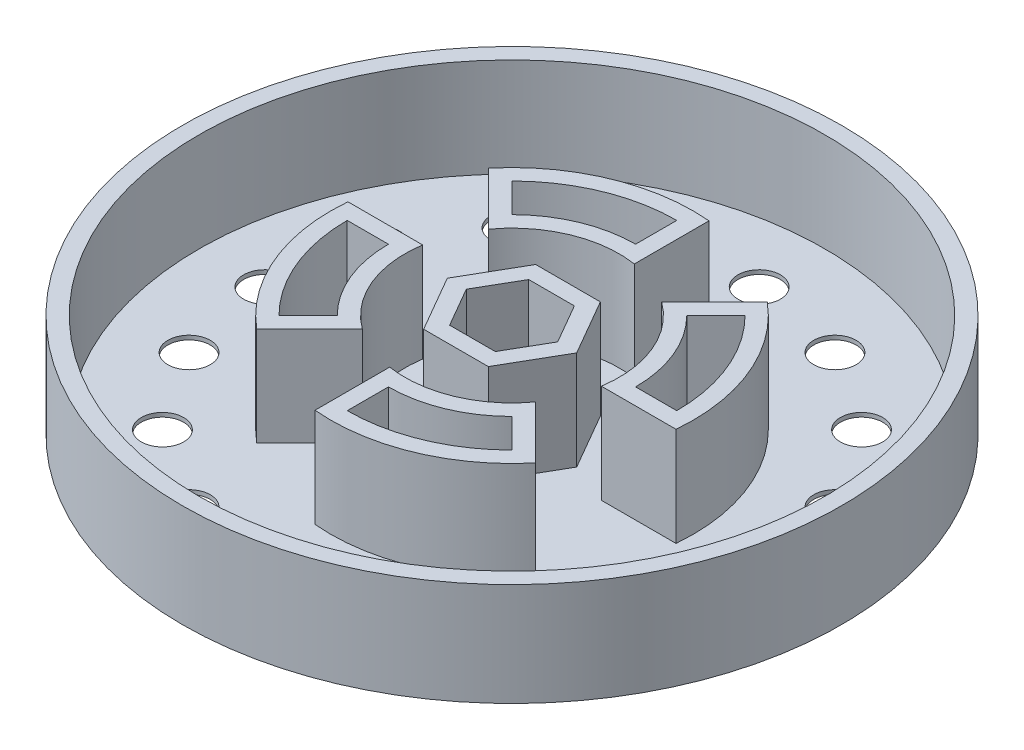
SolidWorks part; units mm, degrees
ref_plane "Front Plane" through (0, 0, 0) normal (0, 0, 1) x (1, 0, 0)
ref_plane "Top Plane" through (0, 0, 0) normal (0, 1, 0) x (1, 0, 0)
ref_plane "Right Plane" through (0, 0, 0) normal (1, 0, 0) x (0, 0, -1)
sketch "Sketch1" plane through (0, 0, 0) normal (0, 1, 0) x (1, 0, 0)
  circle A0 centre (0, 0) radius 50.8
  dimension "D1" = 101.6
extrude "Boss-Extrude1" add sketch "Sketch1" along normal blind 15.875
sketch "Sketch4" plane through (0, 15.875, 0) normal (0, 1, 0) x (1, 0, 0)
  line L0 (-3.5195, 6.096) -> (3.5195, 6.096)
  line L1 (3.5195, 6.096) -> (7.0391, 0)
  line L2 (7.0391, 0) -> (3.5195, -6.096)
  line L3 (3.5195, -6.096) -> (-3.5195, -6.096)
  line L4 (-3.5195, -6.096) -> (-7.0391, 0)
  line L5 (-7.0391, 0) -> (-3.5195, 6.096)
  point P7 (0, 6.096)
  dimension "D1" = 120
  dimension "D2" = 12.192
extrude "Cut-Extrude2" cut sketch "Sketch4" against normal blind 15.24 contours L5 L0 L1 L2 L3 L4
sketch "Sketch5" plane through (0, 0.635, 0) normal (0, 1, 0) x (1, 0, 0)
  circle A0 centre (0, 0) radius 4.191
  dimension "D1" = 8.382
extrude "Cut-Extrude3" cut sketch "Sketch5" against normal through all contours A0
sketch "Sketch6" plane through (0, 15.875, 0) normal (0, 1, 0) x (1, 0, 0)
  line L0 (0, 0) -> (0, 25.4)
  line L1 (0, 0) -> (17.9605, 17.9605)
  line L2 (0, 0) -> (25.4, 0)
  line L3 (0, 0) -> (17.9605, -17.9605)
  line L4 (0, 0) -> (0, -25.4)
  line L5 (0, 0) -> (-17.9605, -17.9605)
  line L6 (0, 0) -> (-25.4, 0)
  line L7 (0, 0) -> (-17.9605, 17.9605)
  circle A0 centre (0, 0) radius 25.4
  circle A1 centre (0, 0) radius 19.05
  point P15 (0, 0)
  dimension "D1" = 38.1
  dimension "D2" = 50.8
  dimension "D3" = 45
  dimension "D4" = 4
extrude "Cut-Extrude4" cut sketch "Sketch6" against normal through all contours A1 L0 A0 L7 | A1 L2 A0 L1 | A1 L4 A0 L3 | A1 L6 A0 L5 region at (-8.3446, 15.875, -20.1456) region at (20.1456, 15.875, -8.3446) region at (8.3446, 15.875, 20.1456) region at (-20.1456, 15.875, 8.3446)
sketch "Sketch7" plane through (0, 15.875, 0) normal (0, 1, 0) x (1, 0, 0)
  line L27 (16.3134, -2.54) -> (27.8243, -2.54)
  line L28 (17.8787, 21.4708) -> (9.7393, 13.3314)
  line L29 (2.54, 16.3134) -> (2.54, 27.8243)
  line L30 (-21.4708, 17.8787) -> (-13.3314, 9.7393)
  line L31 (2.54, 16.3134) -> (2.54, 27.8243)
  line L32 (-21.4708, 17.8787) -> (-13.3314, 9.7393)
  line L33 (-2.54, -16.3134) -> (-2.54, -27.8243)
  line L34 (21.4708, -17.8787) -> (13.3314, -9.7393)
  line L35 (-16.3134, 2.54) -> (-27.8243, 2.54)
  line L36 (-17.8787, -21.4708) -> (-9.7393, -13.3314)
  line L64 (9.972, 0) -> (4.986, 8.636)
  line L65 (4.986, -8.636) -> (9.972, 0)
  line L66 (-4.986, -8.636) -> (4.986, -8.636)
  line L67 (-9.972, 0) -> (-4.986, -8.636)
  line L68 (-4.986, 8.636) -> (-9.972, 0)
  line L69 (4.986, 8.636) -> (-4.986, 8.636)
  line L70 (9.972, 0) -> (4.986, 8.636)
  line L71 (4.986, -8.636) -> (9.972, 0)
  line L72 (-4.986, -8.636) -> (4.986, -8.636)
  line L73 (-9.972, 0) -> (-4.986, -8.636)
  line L74 (-4.986, 8.636) -> (-9.972, 0)
  line L75 (4.986, 8.636) -> (-4.986, 8.636)
  arc A28 (27.8243, -2.54) -> (17.8787, 21.4708) centre (0, 0) ccw
  arc A29 (16.3134, -2.54) -> (9.7393, 13.3314) centre (0, 0) ccw
  arc A30 (2.54, 16.3134) -> (-13.3314, 9.7393) centre (0, 0) ccw
  arc A31 (2.54, 27.8243) -> (-21.4708, 17.8787) centre (0, 0) ccw
  arc A32 (2.54, 16.3134) -> (-13.3314, 9.7393) centre (0, 0) ccw
  arc A33 (2.54, 27.8243) -> (-21.4708, 17.8787) centre (0, 0) ccw
  arc A34 (-2.54, -27.8243) -> (21.4708, -17.8787) centre (0, 0) ccw
  arc A35 (-2.54, -16.3134) -> (13.3314, -9.7393) centre (0, 0) ccw
  arc A36 (-27.8243, 2.54) -> (-17.8787, -21.4708) centre (0, 0) ccw
  arc A37 (-16.3134, 2.54) -> (-9.7393, -13.3314) centre (0, 0) ccw
  circle A40 centre (0, 0) radius 48.26
  circle A41 centre (0, 0) radius 50.8 construction
  point P15 (0, 0)
  dimension "D4" = 2.54
  dimension "D1" = 2.54
  dimension "D3" = 2.54
  dimension "D2" = 4
extrude "Cut-Extrude5" cut sketch "Sketch7" against normal up to surface (15.24 mm away) contours A40 L35 A37 L36 A36 L27 A29 L28 A28 L75 L70 L71 L72 L73 L74 A33 L31 A32 L32 L33 A35 L34 A34 region at (-46.895, 15.875, 0) up to face at (0, 0.635, 4.191)
sketch "Sketch8" plane through (0, 0, 0) normal (0, -1, 0) x (1, 0, 0)
  line L0 (0, 0) -> (0, 25.4) construction
  line L1 (0, 0) -> (-17.9605, 17.9605) construction
  line L2 (-14.5802, 35.1998) -> (0, 0) construction
  circle A0 centre (-14.5802, 35.1998) radius 3.2639
  circle A4 centre (0, 38.1) radius 3.2639
  circle A5 centre (14.5802, 35.1998) radius 3.2639
  circle A6 centre (26.9408, 26.9408) radius 3.2639
  circle A7 centre (35.1998, 14.5802) radius 3.2639
  circle A8 centre (38.1, 0) radius 3.2639
  circle A9 centre (35.1998, -14.5802) radius 3.2639
  circle A10 centre (26.9408, -26.9408) radius 3.2639
  circle A11 centre (14.5802, -35.1998) radius 3.2639
  circle A12 centre (0, -38.1) radius 3.2639
  circle A13 centre (-14.5802, -35.1998) radius 3.2639
  circle A14 centre (-26.9408, -26.9408) radius 3.2639
  circle A15 centre (-35.1998, -14.5802) radius 3.2639
  circle A16 centre (-38.1, 0) radius 3.2639
  circle A17 centre (-35.1998, 14.5802) radius 3.2639
  circle A18 centre (-26.9408, 26.9408) radius 3.2639
  point P17 (0, 0)
  dimension "D1" = 6.5278
  dimension "D2" = 22.5
  dimension "D3" = 38.1
  dimension "D4" = 16
extrude "Cut-Extrude6" cut sketch "Sketch8" against normal through all contours A6 | A4 | A5 | A7 | A8 | A9 | A10 | A11 | A12 | A13 | A14 | A15 | A16 | A17 | A18 | A0 region at (0, 0, 38.1) region at (14.5802, 0, 35.1998) region at (26.9408, 0, 26.9408) region at (35.1998, 0, 14.5802) region at (38.1, 0, 0) region at (35.1998, 0, -14.5802) region at (26.9408, 0, -26.9408) region at (14.5802, 0, -35.1998) region at (0, 0, -38.1) region at (-14.5802, 0, -35.1998) region at (-26.9408, 0, -26.9408) region at (-35.1998, 0, -14.5802) region at (-38.1, 0, 0) region at (-35.1998, 0, 14.5802) region at (-26.9408, 0, 26.9408)
